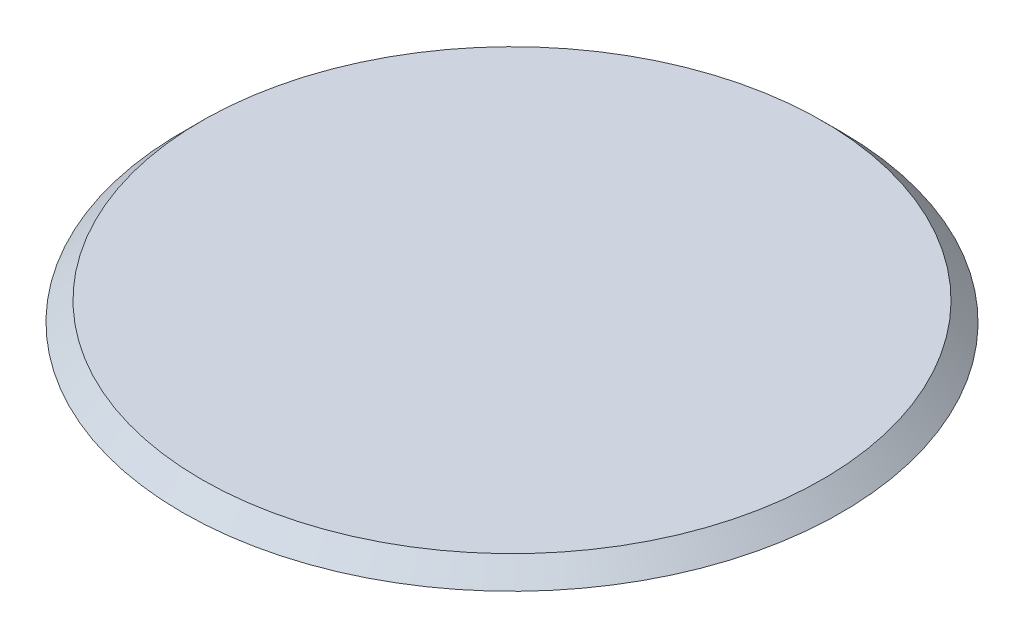
SolidWorks part; units mm, degrees
material "Glass"
ref_plane "正面" through (0, 0, 0) normal (0, 0, 1) x (1, 0, 0)
ref_plane "平面" through (0, 0, 0) normal (0, 1, 0) x (1, 0, 0)
ref_plane "右側面" through (0, 0, 0) normal (1, 0, 0) x (0, 0, -1)
sketch "Sketch1" plane through (0, 0, 0) normal (0, 1, 0) x (1, 0, 0)
  circle A0 centre (0, 0) radius 3.45
extrude "Boss-Extrude1" add sketch "Sketch1" along normal blind 0.2
chamfer "Chamfer1" distance 0.2 angle 45 1 edges at (0, 0.2, 3.45)
